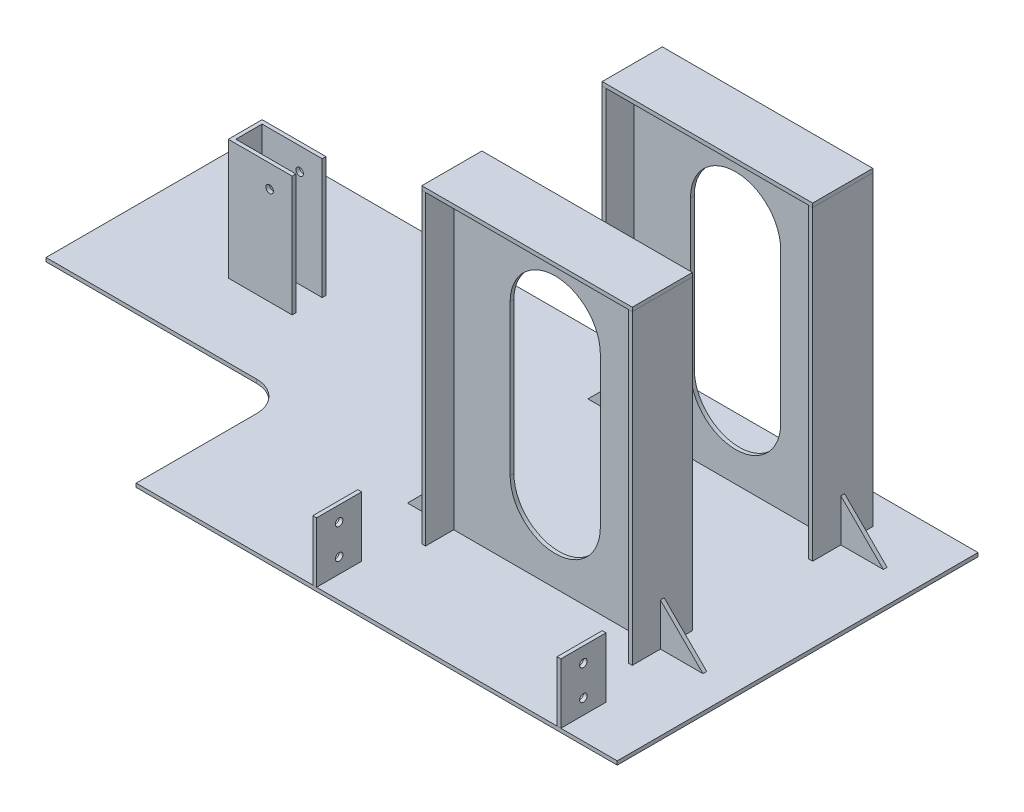
SolidWorks part; units mm, degrees
ref_plane "Front Plane" through (0, 0, 0) normal (0, 0, 1) x (1, 0, 0)
ref_plane "Top Plane" through (0, 0, 0) normal (0, 1, 0) x (1, 0, 0)
ref_plane "Right Plane" through (0, 0, 0) normal (1, 0, 0) x (0, 0, -1)
ref_plane "Back_of bearing" through (0, 0, 101.6) normal (0, 0, 1) x (1, 0, 0)
ref_plane "outside mount" through (88.9, 0, 0) normal (1, 0, 0) x (0, 0, -1)
ref_plane "Load_cell_plane" through (-330.2, 0, 0) normal (1, 0, 0) x (0, 0, -1)
ref_plane "Shaft_centerline plane" through (0, 304.8, 0) normal (0, 1, 0) x (1, 0, 0)
ref_plane "T_slot_outside_face_plane" through (101.6, 0, 0) normal (1, 0, 0) x (0, 0, -1)
ref_plane "Torque_arm_plane" through (0, 0, 25.4) normal (0, 0, 1) x (1, 0, 0)
sketch "Sketch2" plane through (0, 0, 0) normal (0, 1, 0) x (1, 0, 0)
  line L1 (-457.2, 76.2) -> (152.4, 76.2)
  line L2 (-457.2, 76.2) -> (-457.2, -228.6)
  line L3 (-457.2, -228.6) -> (152.4, -228.6)
  line L4 (152.4, 76.2) -> (152.4, -228.6)
  dimension "D1" = 304.8
  dimension "D2" = 609.6
  dimension "D3" = 152.4
  dimension "D4" = 76.2
extrude "Boss-Extrude1" add sketch "Sketch2" against normal blind 3.175
sketch "Sketch3" plane through (88.9, 0, 0) normal (1, 0, 0) x (0, 0, -1)
  line L0 (-101.6, 145.8817) -> (-101.6, -145.8817) construction
  line L1 (-152.4, 0) -> (-101.6, 0)
  line L2 (-152.4, 0) -> (-152.4, 258.7625)
  line L3 (-152.4, 258.7625) -> (-101.6, 258.7625)
  line L4 (-101.6, 0) -> (-101.6, 258.7625)
  line L5 (76.2, 0) -> (-228.6, 0) construction
  line L6 (167.64, 304.8) -> (-167.64, 304.8) construction
  dimension "D1" = 46.0375
  dimension "D2" = 50.8
extrude "Boss-Extrude2" add sketch "Sketch3" against normal blind 3.302 separate body
ref_plane "Plane9" through (-88.9, 0, 0) normal (1, 0, 0) x (0, 0, -1)
sketch "Sketch6" plane through (-88.9, 0, 0) normal (1, 0, 0) x (0, 0, -1)
  line L0 (-101.6, 145.8817) -> (-101.6, -145.8817) construction
  line L1 (-152.4, 258.7625) -> (-101.6, 258.7625)
  line L2 (-152.4, 258.7625) -> (-152.4, 0)
  line L3 (-152.4, 0) -> (-101.6, 0)
  line L4 (-101.6, 258.7625) -> (-101.6, 0)
  line L5 (-228.6, 0) -> (76.2, 0) construction
extrude "Boss-Extrude5" add sketch "Sketch6" along normal blind 3.175 separate body
sketch "Sketch4" plane through (0, 258.7625, 0) normal (0, 1, 0) x (1, 0, 0)
  line L9 (-88.9, -145.8817) -> (-88.9, 145.8817) construction
  line L10 (-88.9, -101.6) -> (88.9, -101.6)
  line L11 (-88.9, -101.6) -> (-88.9, -152.4)
  line L12 (-88.9, -152.4) -> (88.9, -152.4)
  line L13 (88.9, -101.6) -> (88.9, -152.4)
  line L14 (-145.8817, -101.6) -> (145.8817, -101.6) construction
  line L15 (88.9, -145.8817) -> (88.9, 145.8817) construction
  line L16 (85.598, -152.4) -> (88.9, -152.4) construction
extrude "Boss-Extrude3" add sketch "Sketch4" along normal blind 3.302 separate body
ref_plane "Plane6" through (0, 0, 127) normal (0, 0, 1) x (1, 0, 0)
sketch "Sketch5" plane through (0, 0, 127) normal (0, 0, 1) x (1, 0, 0)
  line L1 (-85.725, 258.7625) -> (85.598, 258.7625)
  line L2 (-85.725, 258.7625) -> (-85.725, 0)
  line L3 (-85.725, 0) -> (85.598, 0)
  line L4 (85.598, 258.7625) -> (85.598, 0)
  line L5 (-457.2, 0) -> (152.4, 0) construction
  line L6 (85.598, 258.7625) -> (85.598, 0) construction
extrude "Boss-Extrude4" add sketch "Sketch5" along normal mid plane 3.175 separate body
ref_plane "Plane7" through (0, 0, 50.8) normal (0, 0, 1) x (1, 0, 0)
mirror "Mirror4" about plane through (0, 0, 50.8) normal (0, 0, 1) of bodies 105 102 104 106
ref_plane "Plane11" through (0, 0, 38.1) normal (0, 0, 1) x (1, 0, 0)
sketch "Sketch8" plane through (0, 0, 38.1) normal (0, 0, 1) x (1, 0, 0)
  line L0 (-457.2, 0) -> (152.4, 0) construction
  line L1 (-311.15, 0) -> (-361.95, 0)
  line L2 (-311.15, 0) -> (-311.15, 101.6)
  line L3 (-311.15, 101.6) -> (-361.95, 101.6)
  line L4 (-361.95, 0) -> (-361.95, 101.6)
  line L5 (-330.2, -145.8817) -> (-330.2, 145.8817) construction
  circle A0 centre (-330.2, 82.55) radius 3.175
  dimension "D5" = 6.35
  dimension "D1" = 101.6
  dimension "D2" = 50.8
  dimension "D3" = 19.05
  dimension "D4" = 19.05
extrude "Boss-Extrude6" add sketch "Sketch8" along normal mid plane 3.175 separate body
mirror "Mirror5" about plane through (0, 0, 25.4) normal (0, 0, 1) of bodies 111
sketch "Sketch9" plane through (-361.95, 0, 0) normal (-1, 0, 0) x (0, 0, 1)
  line L1 (11.1125, 101.6) -> (39.6875, 101.6)
  line L2 (11.1125, 101.6) -> (11.1125, 0)
  line L3 (11.1125, 0) -> (39.6875, 0)
  line L4 (39.6875, 101.6) -> (39.6875, 0)
extrude "Boss-Extrude7" add sketch "Sketch9" along normal blind 3.175
sketch "Sketch10" plane through (0, 0, 127) normal (0, 0, 1) x (1, 0, 0)
  line L0 (88.9, 35.921) -> (124.821, 0)
  line L1 (88.9, 258.7625) -> (88.9, 0) construction
  line L2 (-457.2, 0) -> (152.4, 0) construction
  line L3 (124.821, 0) -> (88.9, 0)
  line L4 (88.9, 0) -> (88.9, 35.921)
extrude "Boss-Extrude8" add sketch "Sketch10" along normal mid plane 3.175 separate body
mirror "Mirror6" about plane through (0, 0, 50.8) normal (0, 0, 1) of bodies 114
mirror "Mirror7" about plane through (0, 0, 0) normal (1, 0, 0) of bodies 114 115
sketch "Sketch11" plane through (0, 0, 128.5875) normal (0, 0, 1) x (1, 0, 0)
  line L0 (0, 63.5) -> (0, 190.5) construction
  line L1 (-38.1, 63.5) -> (-38.1, 190.5)
  line L2 (38.1, 63.5) -> (38.1, 190.5)
  arc A0 (-38.1, 63.5) -> (38.1, 63.5) centre (0, 63.5) ccw
  arc A1 (38.1, 190.5) -> (-38.1, 190.5) centre (0, 190.5) ccw
  point P3 (0, 127)
  dimension "D1" = 76.2
  dimension "D2" = 127
  dimension "D3" = 63.5
extrude "Cut-Extrude1" cut sketch "Sketch11" against normal through all
sketch "Sketch12" plane through (0, 0, 0) normal (0, 1, 0) x (1, 0, 0)
  line L1 (-457.2, -228.6) -> (-254, -228.6)
  line L2 (-457.2, -228.6) -> (-457.2, -101.6)
  line L3 (-457.2, -101.6) -> (-279.4, -101.6)
  line L4 (-254, -228.6) -> (-254, -127)
  arc A0 (-279.4, -101.6) -> (-254, -127) centre (-279.4, -127) cw
  point P7 (-254, -101.6)
  dimension "D3" = 25.4
  dimension "D1" = 203.2
  dimension "D2" = 127
extrude "Cut-Extrude2" cut sketch "Sketch12" against normal through all
sketch "Sketch13" plane through (101.6, 0, 0) normal (1, 0, 0) x (0, 0, -1)
  line L1 (-228.6, 0) -> (-190.5, 0)
  line L2 (-228.6, 0) -> (-228.6, 50.8)
  line L3 (-228.6, 50.8) -> (-190.5, 50.8)
  line L4 (-190.5, 0) -> (-190.5, 50.8)
  circle A0 centre (-209.55, 38.1) radius 3.175
  circle A1 centre (-209.55, 12.7) radius 3.175
  point P10 (-209.55, 50.8)
  dimension "D3" = 6.35
  dimension "D1" = 38.1
  dimension "D2" = 50.8
  dimension "D4" = 25.4
  dimension "D5" = 12.7
extrude "Boss-Extrude9" add sketch "Sketch13" along normal blind 3.175 separate body
mirror "Mirror8" about plane through (0, 0, 0) normal (1, 0, 0) of bodies 121
ref_axis "Axis1" through (0, 304.8, 1444.9505) along (0, 0, -1)
sketch "Sketch14" plane through (0, 262.0645, 0) normal (0, 1, 0) x (1, 0, 0)
  line L0 (58.3406, -117.7356) -> (62.3094, -117.7356) construction
  line L9 (62.3094, -134.4044) -> (58.3406, -134.4044) construction
  line L15 (-58.3406, -134.4044) -> (-62.3094, -134.4044) construction
  line L16 (-62.3094, -117.7356) -> (-58.3406, -117.7356) construction
  line L25 (62.3094, 16.5415) -> (58.3406, 16.5415) construction
  line L26 (58.3406, 33.2102) -> (62.3094, 33.2102) construction
  line L35 (-58.3406, 16.5415) -> (-62.3094, 16.5415) construction
  line L36 (-62.3094, 33.2102) -> (-58.3406, 33.2102) construction
  line L40 (58.3406, -117.7356) -> (62.3094, -117.7356)
  line L49 (62.3094, -134.4044) -> (58.3406, -134.4044)
  line L55 (-58.3406, -134.4044) -> (-62.3094, -134.4044)
  line L56 (-62.3094, -117.7356) -> (-58.3406, -117.7356)
  line L65 (62.3094, 16.5415) -> (58.3406, 16.5415)
  line L66 (58.3406, 33.2102) -> (62.3094, 33.2102)
  line L75 (-58.3406, 16.5415) -> (-62.3094, 16.5415)
  line L76 (-62.3094, 33.2102) -> (-58.3406, 33.2102)
  arc A0 (58.3406, -117.7356) -> (50.0062, -126.07) centre (58.3406, -126.07) ccw construction
  arc A1 (70.6437, -126.07) -> (62.3094, -117.7356) centre (62.3094, -126.07) ccw construction
  arc A2 (50.0062, -126.07) -> (58.3406, -134.4044) centre (58.3406, -126.07) ccw construction
  arc A3 (62.3094, -134.4044) -> (70.6437, -126.07) centre (62.3094, -126.07) ccw construction
  arc A4 (-70.6437, -126.07) -> (-62.3094, -134.4044) centre (-62.3094, -126.07) ccw construction
  arc A5 (-58.3406, -134.4044) -> (-50.0062, -126.07) centre (-58.3406, -126.07) ccw construction
  arc A6 (-62.3094, -117.7356) -> (-70.6437, -126.07) centre (-62.3094, -126.07) ccw construction
  arc A7 (-50.0062, -126.07) -> (-58.3406, -117.7356) centre (-58.3406, -126.07) ccw construction
  arc A8 (50.0062, 24.8758) -> (58.3406, 16.5415) centre (58.3406, 24.8758) ccw construction
  arc A9 (62.3094, 16.5415) -> (70.6437, 24.8758) centre (62.3094, 24.8758) ccw construction
  arc A10 (58.3406, 33.2102) -> (50.0062, 24.8758) centre (58.3406, 24.8758) ccw construction
  arc A11 (70.6437, 24.8758) -> (62.3094, 33.2102) centre (62.3094, 24.8758) ccw construction
  arc A12 (-70.6437, 24.8758) -> (-62.3094, 16.5415) centre (-62.3094, 24.8758) ccw construction
  arc A13 (-58.3406, 16.5415) -> (-50.0062, 24.8758) centre (-58.3406, 24.8758) ccw construction
  arc A14 (-62.3094, 33.2102) -> (-70.6437, 24.8758) centre (-62.3094, 24.8758) ccw construction
  arc A15 (-50.0062, 24.8758) -> (-58.3406, 33.2102) centre (-58.3406, 24.8758) ccw construction
  arc A16 (58.3406, -117.7356) -> (50.0062, -126.07) centre (58.3406, -126.07) ccw
  arc A17 (70.6437, -126.07) -> (62.3094, -117.7356) centre (62.3094, -126.07) ccw
  arc A18 (50.0062, -126.07) -> (58.3406, -134.4044) centre (58.3406, -126.07) ccw
  arc A19 (62.3094, -134.4044) -> (70.6437, -126.07) centre (62.3094, -126.07) ccw
  arc A20 (-70.6437, -126.07) -> (-62.3094, -134.4044) centre (-62.3094, -126.07) ccw
  arc A21 (-58.3406, -134.4044) -> (-50.0062, -126.07) centre (-58.3406, -126.07) ccw
  arc A22 (-62.3094, -117.7356) -> (-70.6437, -126.07) centre (-62.3094, -126.07) ccw
  arc A23 (-50.0062, -126.07) -> (-58.3406, -117.7356) centre (-58.3406, -126.07) ccw
  arc A24 (50.0062, 24.8758) -> (58.3406, 16.5415) centre (58.3406, 24.8758) ccw
  arc A25 (62.3094, 16.5415) -> (70.6437, 24.8758) centre (62.3094, 24.8758) ccw
  arc A26 (58.3406, 33.2102) -> (50.0062, 24.8758) centre (58.3406, 24.8758) ccw
  arc A27 (70.6437, 24.8758) -> (62.3094, 33.2102) centre (62.3094, 24.8758) ccw
  arc A28 (-70.6437, 24.8758) -> (-62.3094, 16.5415) centre (-62.3094, 24.8758) ccw
  arc A29 (-58.3406, 16.5415) -> (-50.0062, 24.8758) centre (-58.3406, 24.8758) ccw
  arc A30 (-62.3094, 33.2102) -> (-70.6437, 24.8758) centre (-62.3094, 24.8758) ccw
  arc A31 (-50.0062, 24.8758) -> (-58.3406, 33.2102) centre (-58.3406, 24.8758) ccw
extrude "Cut-Extrude3" [suppressed] cut sketch "Sketch14" against normal up to surface (3.302 mm away)
equation "\"Bearing_dist\"= 4in"
equation "\"plate_thickness\"= 0.125in"
equation "\"shaft_centerline_h\"= 12in"
equation "\"torque_arm_l\"= 13in"
equation "\"mount_width\"= 7in"
equation "\"gusset_throat\"= 2in"
equation "\"T_slot_outside_width\"= 8in"
equation "\"D1@outside mount\" = \"mount_width\" / 2"
equation "\"D1@Boss-Extrude1\"=\"plate_thickness\""
equation "\"D1@Boss-Extrude4\"=\"plate_thickness\""
equation "\"D1@Boss-Extrude5\"=\"plate_thickness\""
equation "\"Torque_arm_center\"= 3in"
equation "\"D1@Torque_arm_plane\" = \"Torque_arm_center\""
equation "\"D1@Back_of bearing\"=\"Bearing_dist\""
equation "\"D1@Load_cell_plane\"=\"torque_arm_l\""
equation "\"D1@Shaft_centerline plane\"=\"shaft_centerline_h\""
equation "\"D1@T_slot_outside_face_plane\"=\"T_slot_outside_width\"/2"
equation "\"D1@Boss-Extrude6\"=\"plate_thickness\""
equation "\"D1@Boss-Extrude7\"=\"plate_thickness\""
equation "\"D1@Sketch10\"=\"gusset_throat\""
equation "\"D1@Boss-Extrude8\"=\"plate_thickness\""
equation "\"D1@Boss-Extrude9\"=\"plate_thickness\""
equation "\"D1@Sketch3\"=\"plate_thickness\"+1.6875"
